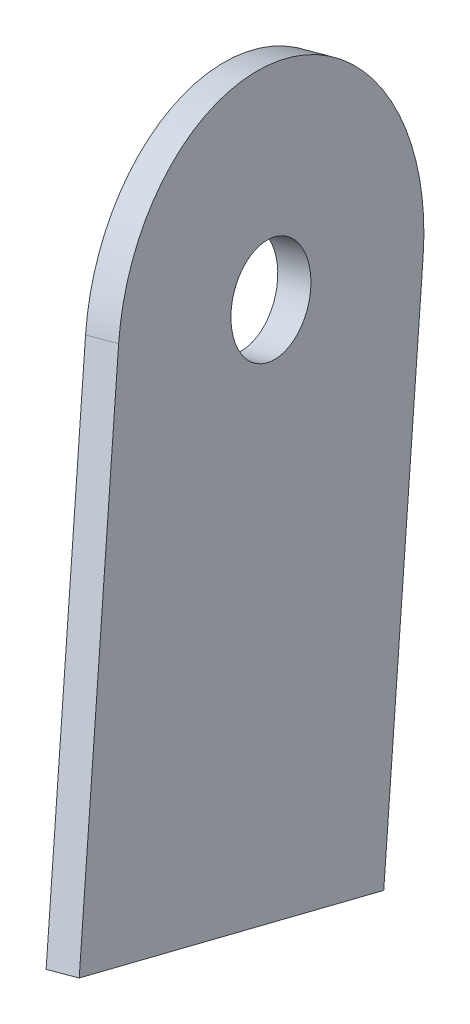
SolidWorks part; units mm, degrees
ref_plane "Front Plane" through (0, 0, 0) normal (0, 0, 1) x (1, 0, 0)
ref_plane "Top Plane" through (0, 0, 0) normal (0, 1, 0) x (1, 0, 0)
ref_plane "Right Plane" through (0, 0, 0) normal (1, 0, 0) x (0, 0, -1)
sketch "Sketch1" plane through (434.7276, 72.5148, -64.236) normal (0.9761, 0.1628, -0.1442) x (-0.1423, -0.0237, -0.9895)
  line L0 (387.2863, 214.3907) -> (387.5958, 208.7858) construction
  line L1 (378.3138, 214.312) -> (371.1536, 190.3182)
  line L2 (371.1536, 190.3182) -> (389.4081, 184.8707)
  line L3 (389.4081, 184.8707) -> (396.5683, 208.8645)
  line L4 (73.9979, 278.9949) -> (458.87, 164.142) construction
  circle A0 centre (387.441, 211.5883) radius 2.4892
  circle A1 centre (384.4588, 265.608) radius 2.4892 construction
  arc A2 (396.5683, 208.8645) -> (378.3138, 214.312) centre (387.441, 211.5883) ccw
  point P10 (388.9939, 181.0647)
  dimension "D1" = 19.05
extrude "Boss-Extrude1" add sketch "Sketch1" along normal blind 1.5875
